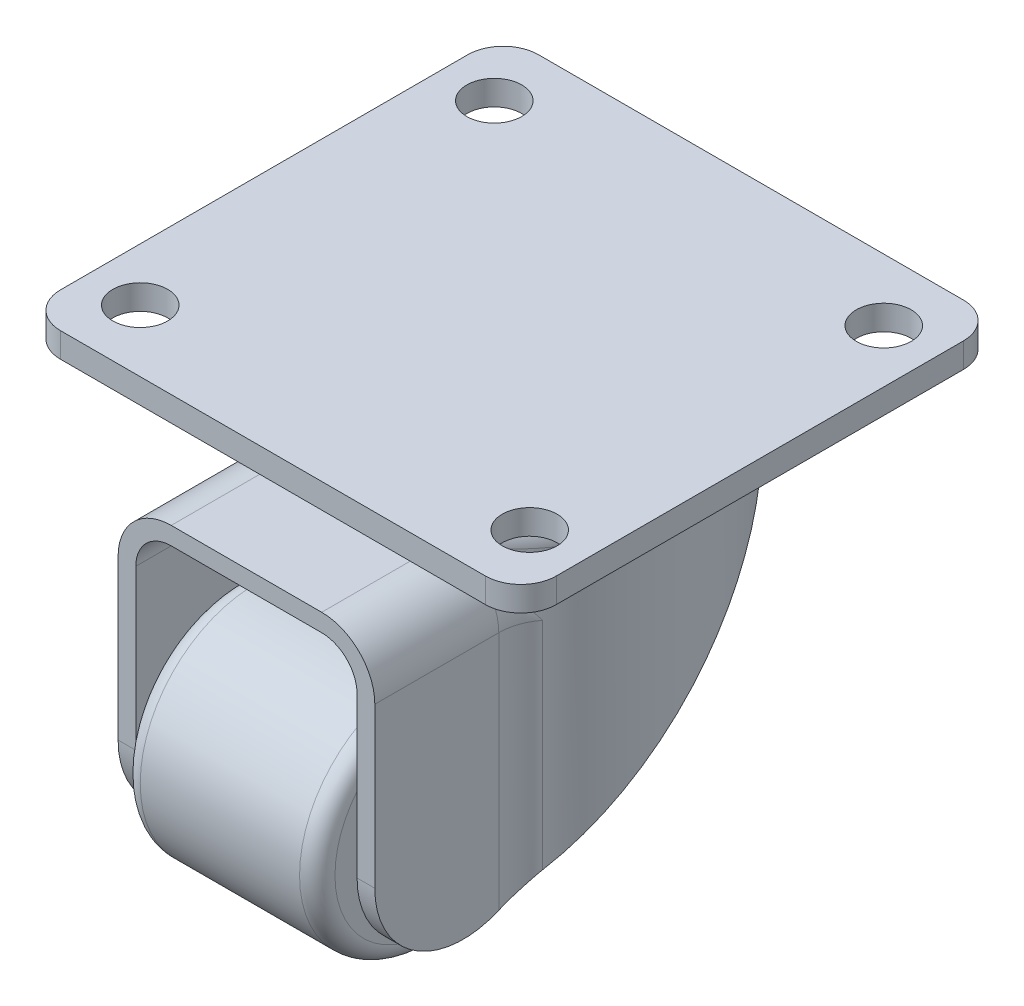
SolidWorks part; units mm, degrees
ref_plane "Front Plane" through (0, 0, 0) normal (0, 0, 1) x (1, 0, 0)
ref_plane "Top Plane" through (0, 0, 0) normal (0, 1, 0) x (1, 0, 0)
ref_plane "Right Plane" through (0, 0, 0) normal (1, 0, 0) x (0, 0, -1)
sketch "Sketch1" plane through (0, 0, 0) normal (0, 1, 0) x (1, 0, 0)
  line L1 (14, -13.5) -> (-14, -13.5)
  line L2 (14, -13.5) -> (14, 13.5)
  line L3 (14, 13.5) -> (-14, 13.5)
  line L4 (-14, -13.5) -> (-14, 13.5)
  line L5 (14, -13.5) -> (-14, 13.5) construction
  line L6 (14, 13.5) -> (-14, -13.5) construction
  point P0 (0, 0)
  dimension "D1" = 28
  dimension "D2" = 27
extrude "Boss-Extrude1" add sketch "Sketch1" along normal blind 1.4
sketch "Sketch2" plane through (0, 1.4, 0) normal (0, 1, 0) x (1, 0, 0)
  line L1 (11, -10) -> (-11, -10) construction
  line L2 (11, -10) -> (11, 10) construction
  line L3 (11, 10) -> (-11, 10) construction
  line L4 (-11, -10) -> (-11, 10) construction
  line L5 (11, -10) -> (-11, 10) construction
  line L6 (11, 10) -> (-11, -10) construction
  circle A0 centre (-11, 10) radius 1.55
  circle A1 centre (-11, -10) radius 1.55
  circle A2 centre (11, -10) radius 1.55
  circle A3 centre (11, 10) radius 1.55
  point P0 (0, 0)
  dimension "D1" = 3.1
  dimension "D2" = 22
  dimension "D3" = 20
extrude "Cut-Extrude1" cut sketch "Sketch2" against normal through all
fillet "Fillet1" radius 2 4 edges at (-14, 0.7, -13.5) (14, 0.7, -13.5) (14, 0.7, 13.5) (-14, 0.7, 13.5)
sketch "Sketch3" plane through (0, 0, 0) normal (1, 0, 0) x (0, 0, -1)
  line L0 (0, 0) -> (0, -4.5)
  line L1 (0, -4.5) -> (10, -4.5)
  line L2 (10, -4.5) -> (10, -2.0338)
  line L3 (10, -2.0338) -> (8.7679, -1)
  line L4 (8.7679, -1) -> (10.5, 0)
  line L5 (-11.5, 0) -> (11.5, 0) construction
  line L6 (10.5, 0) -> (0, 0)
  dimension "D1" = 4.5
  dimension "D2" = 10
  dimension "D3" = 10.5
  dimension "D4" = 3.5
  dimension "D5" = 30
  dimension "D6" = 70
revolve "Revolve1" add sketch "Sketch3" angle 360 about L0
fillet "Fillet2" radius 2 1 edges at (0, -2.0338, 10)
sketch "Sketch4" plane through (0, -4.5, 0) normal (0, -1, 0) x (1, 0, 0)
  line L0 (-7.25, 15) -> (-7.25, 6.8875)
  line L2 (7.25, 15) -> (7.25, 6.8875)
  line L3 (-6.25, 6.4759) -> (-6.25, 15)
  line L5 (6.25, 15) -> (6.25, 6.4759)
  line L6 (-7.25, 15) -> (-6.25, 15)
  line L7 (-6.25, 15) -> (6.25, 15) construction
  line L8 (7.25, 15) -> (6.25, 15)
  line L9 (0, 15) -> (0, 0) construction
  circle A0 centre (0, 0) radius 10 construction
  arc A1 (-7.25, 6.8875) -> (7.25, 6.8875) centre (0, 0) ccw
  arc A2 (-6.25, 6.4759) -> (6.25, 6.4759) centre (0, 0) ccw
  dimension "D1" = 18
  dimension "D2" = 1
  dimension "D3" = 1
  dimension "D4" = 12.5
  dimension "D5" = 15
extrude "Boss-Extrude2" add sketch "Sketch4" along normal blind 20
sketch "Sketch5" plane through (0, 0, 15) normal (0, 0, 1) x (1, 0, 0)
  line L1 (-7.25, -3.5) -> (7.25, -3.5)
  line L2 (-7.25, -3.5) -> (-7.25, -4.5)
  line L3 (-7.25, -4.5) -> (7.25, -4.5)
  line L4 (7.25, -3.5) -> (7.25, -4.5)
  line L5 (-6.25, -24.5) -> (-7.25, -24.5) construction
extrude "Boss-Extrude3" add sketch "Sketch5" against normal blind 20
fillet "Fillet3" radius 4 2 edges at (6.25, -14.5, 6.4759) (-6.25, -14.5, 6.4759)
fillet "Fillet4" radius 3 2 edges at (7.25, -14, 6.8875) (-7.25, -14, 6.8875)
sketch "Sketch6" plane through (0, 0, 0) normal (1, 0, 0) x (0, 0, -1)
  line L0 (10, -4.5) -> (7, -4.5)
  line L1 (10, -24.5) -> (10, -2.9664) construction
  line L2 (7, -4.5) -> (-6.3313, -18.8971)
  line L3 (-6.3313, -18.8971) -> (-15, -15.5) construction
  line L4 (-15, -24.5) -> (-15, -3.5) construction
  line L5 (-15, -15.5) -> (-15, -4.5) construction
  line L6 (-15, -4.5) -> (7, -4.5) construction
  line L7 (-11.5, 0) -> (11.5, 0) construction
  line L8 (-15, -15.5) -> (-15, -24.5)
  line L9 (-15, -24.5) -> (10, -24.5)
  line L10 (10, -24.5) -> (10, -4.5)
  arc A0 (-15, -15.5) -> (-6.3313, -18.8971) centre (-10, -15.5) ccw
  dimension "D1" = 10
  dimension "D2" = 4.5
  dimension "D3" = 15.5
  dimension "D4" = 3
extrude "Cut-Extrude2" cut sketch "Sketch6" against normal through all both and the other way through all
fillet "Fillet6" radius 2 6 edges at (8.9413, -4.5, -1.0266) (6.4674, -4.5, 6.6952) (-8.9413, -4.5, -1.0266) (-6.4674, -4.5, 6.6952) (6.25, -4.5, 11.498) (-6.25, -4.5, 11.498)
fillet "Fillet7" radius 3 4 edges at (7.4131, -3.5, 7.0204) (-7.4131, -3.5, 7.0204) (7.25, -3.5, 11.498) (-7.25, -3.5, 11.498)
sketch "Sketch7" plane through (-7.25, 0, 0) normal (-1, 0, 0) x (0, 0, 1)
  circle A0 centre (10, -15.5) radius 1.25
  dimension "D1" = 2.5
extrude "Boss-Extrude4" add sketch "Sketch7" against normal up to surface (14.5 mm away) up to face at (7.25, -12.6187, 11.8077)
sketch "Sketch8" plane through (0, 0, 0) normal (1, 0, 0) x (0, 0, -1)
  line L0 (-10, -22) -> (0, -22) construction
  line L1 (0, -22) -> (0, 1.4) construction
  line L2 (-11.5, 1.4) -> (11.5, 1.4) construction
  circle A0 centre (-10, -15.5) radius 6.5
  dimension "D1" = 13
  dimension "D2" = 23.4
extrude "Boss-Extrude5" add sketch "Sketch8" along normal mid plane 11
fillet "Fillet8" radius 1 2 edges at (-5.5, -15.5, 3.5) (5.5, -15.5, 3.5)
